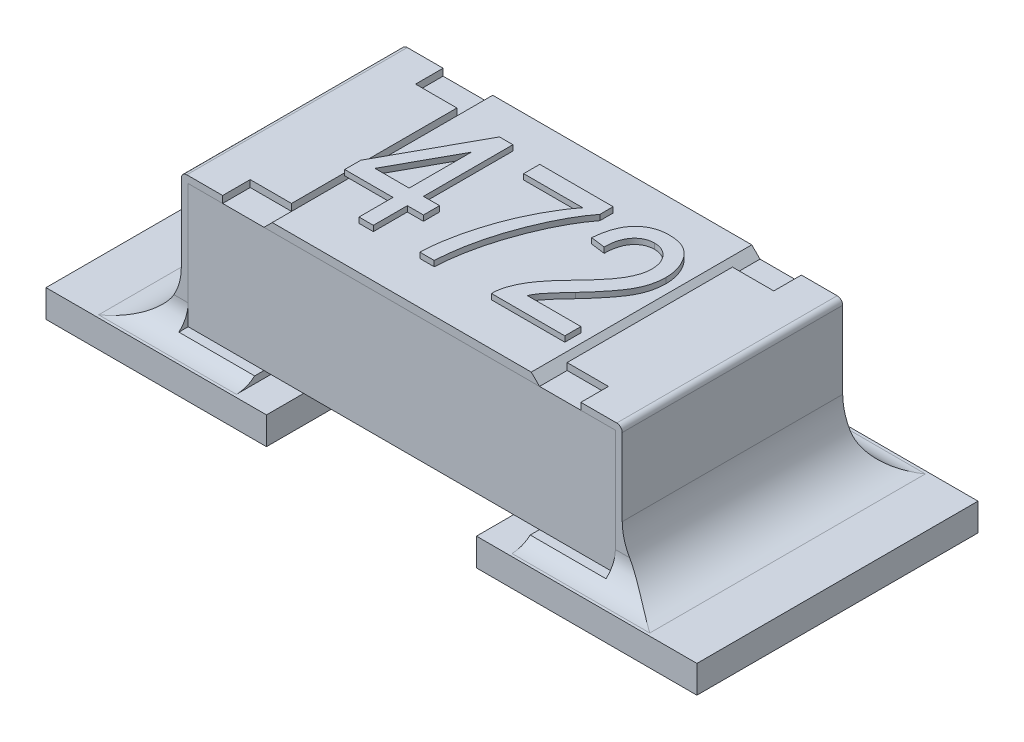
SolidWorks part; units mm, degrees
material "Ceramic Porcelain"
ref_plane "Front Plane" through (0, 0, 0) normal (0, 0, 1) x (1, 0, 0)
ref_plane "Top Plane" through (0, 0, 0) normal (0, 1, 0) x (1, 0, 0)
ref_plane "Right Plane" through (0, 0, 0) normal (1, 0, 0) x (0, 0, -1)
sketch "Sketch1" plane through (0, 0, 0) normal (1, 0, 0) x (0, 0, -1)
  line L0 (0, 55) -> (0, -55) construction
  line L1 (-0.4, 0.575) -> (0.4, 0.575)
  line L2 (-0.4, 0.575) -> (-0.4, 0.125)
  line L3 (-0.4, 0.125) -> (0.4, 0.125)
  line L4 (0.4, 0.575) -> (0.4, 0.125)
  line L5 (55, 0) -> (-55, 0) construction
  dimension "D1" = 0.8
  dimension "D2" = 0.4
  dimension "D3" = 0.45
  dimension "D4" = 0.125
extrude "Boss-Extrude1" add sketch "Sketch1" along normal mid plane 1.55
sketch "Sketch2" plane through (0, 0, 0) normal (0, 0, 1) x (1, 0, 0)
  line L0 (-0.5, 0.6) -> (-0.78, 0.6)
  line L1 (-0.8, 0.58) -> (-0.8, 0.1)
  line L2 (-0.8, 0.1) -> (-0.5, 0.1)
  line L3 (-0.5, 0.1) -> (-0.5, 0.125)
  line L4 (0.775, 0.125) -> (-0.775, 0.125) construction
  line L5 (-0.5, 0.125) -> (-0.775, 0.125)
  line L6 (-0.775, 0.125) -> (-0.775, 0.575)
  line L7 (-0.775, 0.575) -> (-0.5, 0.575)
  line L8 (0.775, 0.575) -> (-0.775, 0.575) construction
  line L9 (-0.5, 0.575) -> (-0.5, 0.6)
  line L11 (0.5, 0.575) -> (0.5, 0.6)
  line L12 (0.5, 0.6) -> (0.78, 0.6)
  line L13 (0.8, 0.58) -> (0.8, 0.1)
  line L14 (0.8, 0.1) -> (0.5, 0.1)
  line L15 (0.5, 0.1) -> (0.5, 0.125)
  line L16 (0.5, 0.125) -> (0.775, 0.125)
  line L17 (0.775, 0.125) -> (0.775, 0.575)
  line L18 (0.775, 0.575) -> (0.5, 0.575)
  arc A0 (0.78, 0.6) -> (0.8, 0.58) centre (0.78, 0.58) cw
  arc A1 (-0.78, 0.6) -> (-0.8, 0.58) centre (-0.78, 0.58) ccw
  point P28 (-0.8, 0.6)
  dimension "D6" = 0.02
  dimension "D1" = 0.025
  dimension "D2" = 0.025
  dimension "D3" = 0.025
  dimension "D4" = 0.3
  dimension "D5" = 0.3
extrude "Boss-Extrude2" add sketch "Sketch2" along normal mid plane 0.8 separate body
sketch "Sketch3" plane through (0, 0.6, 0) normal (0, 1, 0) x (1, 0, 0)
  line L0 (0.5, -0.4) -> (0.5, 0.4) construction
  line L1 (-0.5, 0.4) -> (-0.65, 0.4)
  line L2 (-0.5, 0.4) -> (-0.5, 0.3)
  line L3 (-0.5, 0.3) -> (-0.65, 0.3)
  line L4 (-0.65, 0.4) -> (-0.65, 0.3)
  line L5 (-0.5, -0.4) -> (-0.65, -0.4)
  line L6 (-0.5, -0.4) -> (-0.5, -0.3)
  line L7 (-0.5, -0.3) -> (-0.65, -0.3)
  line L8 (-0.65, -0.4) -> (-0.65, -0.3)
  line L9 (0.5, -0.4) -> (0.65, -0.4)
  line L10 (0.5, -0.4) -> (0.5, -0.3)
  line L11 (0.5, -0.3) -> (0.65, -0.3)
  line L12 (0.65, -0.4) -> (0.65, -0.3)
  line L13 (0.775, -0.4) -> (-0.775, -0.4) construction
  line L15 (0.5, 0.4) -> (0.65, 0.4)
  line L16 (0.5, 0.4) -> (0.5, 0.3)
  line L17 (0.5, 0.3) -> (0.65, 0.3)
  line L18 (0.65, 0.4) -> (0.65, 0.3)
  dimension "D1" = 0.15
  dimension "D2" = 0.1
extrude "Cut-Extrude1" cut sketch "Sketch3" against normal blind 0.025
sketch "Sketch4" plane through (0, 0, 0) normal (0, 0, 1) x (1, 0, 0)
  line L0 (-0.5, 0.575) -> (0.5, 0.575)
  line L1 (0.5, 0.575) -> (0.47, 0.605)
  line L2 (0.47, 0.605) -> (-0.47, 0.605)
  line L3 (-0.47, 0.605) -> (-0.5, 0.575)
  dimension "D1" = 45
  dimension "D2" = 45
  dimension "D3" = 0.03
extrude "Boss-Extrude3" add sketch "Sketch4" along normal mid plane 0.8 separate body
sketch "Sketch7" plane through (0, 0, 0) normal (0, 1, 0) x (1, 0, 0)
  line L0 (0, -0.2833) -> (0, 0.2833) construction
  line L1 (-0.381, -0.51) -> (-1.181, -0.51)
  line L2 (-0.381, -0.51) -> (-0.381, 0.51)
  line L3 (-0.381, 0.51) -> (-1.181, 0.51)
  line L4 (-1.181, -0.51) -> (-1.181, 0.51)
  line L5 (0.381, -0.51) -> (1.181, -0.51)
  line L6 (0.381, -0.51) -> (0.381, 0.51)
  line L7 (0.381, 0.51) -> (1.181, 0.51)
  line L8 (1.181, -0.51) -> (1.181, 0.51)
  line L9 (-0.2833, 0) -> (0.2833, 0) construction
  dimension "D1" = 0.8
  dimension "D2" = 0.381
  dimension "D3" = 0.381
  dimension "D4" = 1.02
  dimension "D5" = 0.51
extrude "Boss-Extrude5" add sketch "Sketch7" along normal blind 0.1
fillet "Fillet3" radius 0.2 1 edges at (-0.8, 0.1, 0)
fillet "Fillet4" radius 0.2 1 edges at (0.8, 0.1, 0)
fillet "Fillet5" radius 0.1 2 edges at (0.75, 0.1, -0.4) (0.75, 0.1, 0.4)
fillet "Fillet6" radius 0.1 2 edges at (-0.75, 0.1, 0.4) (-0.75, 0.1, -0.4)
sketch "Esquisse2" plane through (0, 0.605, 0) normal (0, 1, 0) x (1, 0, 0)
  text T0 "472\r\n" font "Arial Narrow" height 0.5
extrude "Boss.-Extru.1" add sketch "Esquisse2" along normal blind 0.02
